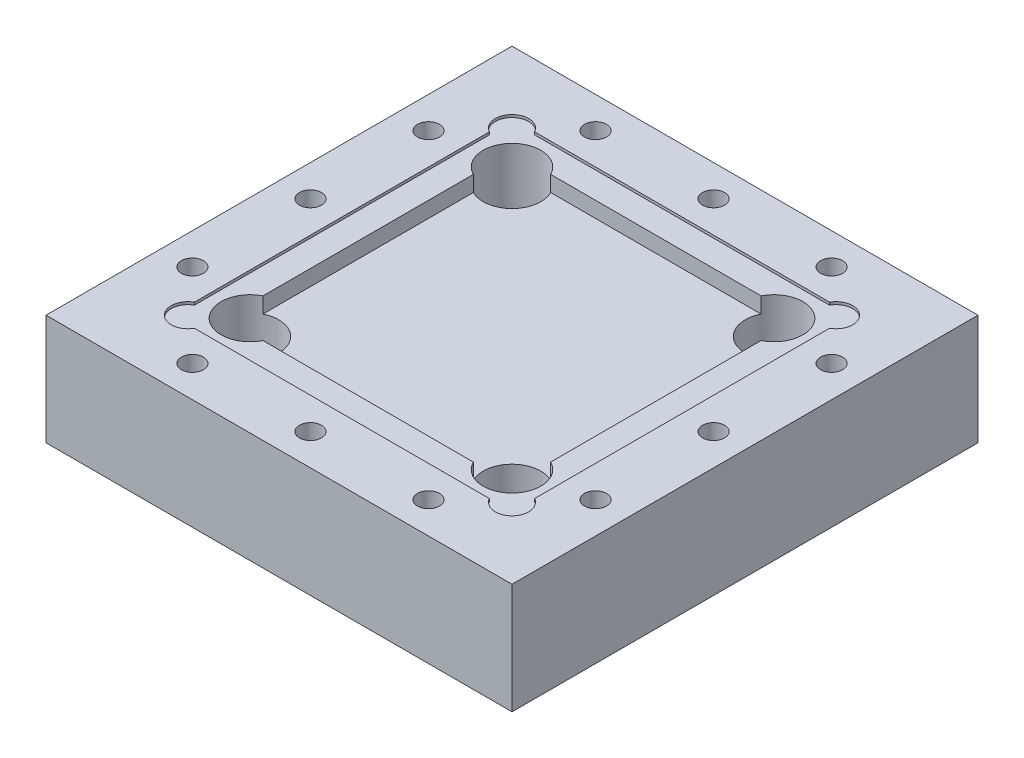
SolidWorks part; units mm, degrees
ref_plane "Front Plane" through (0, 0, 0) normal (0, 0, 1) x (1, 0, 0)
ref_plane "Top Plane" through (0, 0, 0) normal (0, 1, 0) x (1, 0, 0)
ref_plane "Right Plane" through (0, 0, 0) normal (1, 0, 0) x (0, 0, -1)
sketch "Sketch1" plane through (0, 0, 0) normal (0, 1, 0) x (1, 0, 0)
  line L0 (-38.45, 38.45) -> (-22.5235, 38.45) construction
  line L1 (-25, -25) -> (25, -25) construction
  line L2 (-25, -25) -> (-25, 25) construction
  line L3 (-25, 25) -> (25, 25) construction
  line L4 (25, -25) -> (25, 25) construction
  line L5 (-25, -25) -> (25, 25) construction
  line L6 (-25, 25) -> (25, -25) construction
  line L7 (44.45, -44.45) -> (-44.45, -44.45)
  line L8 (44.45, -44.45) -> (44.45, 44.45)
  line L9 (44.45, 44.45) -> (-44.45, 44.45)
  line L10 (-44.45, -44.45) -> (-44.45, 44.45)
  line L11 (44.45, -44.45) -> (-44.45, 44.45) construction
  line L12 (44.45, 44.45) -> (-44.45, -44.45) construction
  line L13 (32.45, -32.45) -> (-32.45, -32.45) construction
  line L14 (32.45, -32.45) -> (32.45, 32.45) construction
  line L15 (32.45, 32.45) -> (-32.45, 32.45) construction
  line L16 (-32.45, -32.45) -> (-32.45, 32.45) construction
  line L17 (32.45, -32.45) -> (-32.45, 32.45) construction
  line L18 (32.45, 32.45) -> (-32.45, -32.45) construction
  line L19 (-22.5235, 38.45) -> (0, 38.45) construction
  line L20 (0, 38.45) -> (22.5235, 38.45) construction
  line L21 (22.5235, 38.45) -> (38.45, 38.45) construction
  line L22 (38.45, 38.45) -> (38.45, 22.5235) construction
  line L23 (38.45, 22.5235) -> (38.45, 0) construction
  line L24 (38.45, 0) -> (38.45, -22.5235) construction
  line L25 (38.45, -22.5235) -> (38.45, -38.45) construction
  line L26 (38.45, -38.45) -> (22.5235, -38.45) construction
  line L27 (22.5235, -38.45) -> (0, -38.45) construction
  line L28 (0, -38.45) -> (-22.5235, -38.45) construction
  line L29 (-22.5235, -38.45) -> (-38.45, -38.45) construction
  line L30 (-38.45, -38.45) -> (-38.45, -22.5235) construction
  line L31 (-38.45, -22.5235) -> (-38.45, 0) construction
  line L32 (-38.45, 0) -> (-38.45, 22.5235) construction
  line L33 (-38.45, 22.5235) -> (-38.45, 38.45) construction
  line L34 (-38.45, 22.5235) -> (-22.5235, 38.45) construction
  line L35 (22.5235, 38.45) -> (38.45, 22.5235) construction
  line L36 (38.45, -22.5235) -> (22.5235, -38.45) construction
  line L37 (-38.45, -22.5235) -> (-22.5235, -38.45) construction
  line L38 (-32.45, 0) -> (-44.45, 0) construction
  line L40 (27.45, -27.45) -> (-27.45, -27.45) construction
  line L41 (27.45, -27.45) -> (27.45, 27.45) construction
  line L42 (27.45, 27.45) -> (-27.45, 27.45) construction
  line L43 (-27.45, -27.45) -> (-27.45, 27.45) construction
  line L44 (27.45, -27.45) -> (-27.45, 27.45) construction
  line L45 (27.45, 27.45) -> (-27.45, -27.45) construction
  circle A0 centre (-25, 25) radius 5 construction
  circle A1 centre (25, 25) radius 5 construction
  circle A2 centre (25, -25) radius 5 construction
  circle A3 centre (-25, -25) radius 5 construction
  circle A4 centre (-22.5235, 38.45) radius 4.25 construction
  circle A5 centre (0, 38.45) radius 4.25 construction
  circle A6 centre (22.5235, 38.45) radius 4.25 construction
  circle A7 centre (38.45, 22.5235) radius 4.25 construction
  circle A8 centre (38.45, 0) radius 4.25 construction
  circle A9 centre (38.45, -22.5235) radius 4.25 construction
  circle A10 centre (22.5235, -38.45) radius 4.25 construction
  circle A11 centre (0, -38.45) radius 4.25 construction
  circle A12 centre (-22.5235, -38.45) radius 4.25 construction
  circle A13 centre (-38.45, -22.5235) radius 4.25 construction
  circle A14 centre (-38.45, 0) radius 4.25 construction
  circle A15 centre (-38.45, 22.5235) radius 4.25 construction
  point P0 (0, 0)
  point P6 (0, 0)
  point P11 (0, 0)
  point P51 (0, 0)
  dimension "D4" = 10
  dimension "D5" = 8.5
  dimension "D1" = 50
  dimension "D2" = 64.9
  dimension "D3" = 12
  dimension "D6" = 5
  dimension "D7" = 88.9
extrude "Boss-Extrude1" add sketch "Sketch1" along normal blind 21.082
sketch "Sketch2" plane through (0, 21.082, 0) normal (0, 1, 0) x (1, 0, 0)
  line L0 (32.45, -32.45) -> (-32.45, -32.45) construction
  line L1 (32.45, -32.45) -> (32.45, 32.45) construction
  line L2 (-32.45, -32.45) -> (-32.45, 32.45) construction
  line L3 (32.45, 32.45) -> (-32.45, 32.45) construction
  line L4 (28.1344, -32.45) -> (-28.1344, -32.45)
  line L5 (32.45, -28.1344) -> (32.45, 28.1344)
  line L6 (-32.45, -28.1344) -> (-32.45, 28.1344)
  line L7 (28.1344, 32.45) -> (-28.1344, 32.45)
  line L8 (44.45, -44.45) -> (-44.45, 44.45) construction
  line L9 (-32.45, 32.45) -> (-33.1571, 33.1571) construction
  line L10 (44.45, 44.45) -> (-44.45, -44.45) construction
  line L11 (32.45, 32.45) -> (33.1571, 33.1571) construction
  line L12 (32.45, -32.45) -> (33.1571, -33.1571) construction
  line L13 (-32.45, -32.45) -> (-33.1571, -33.1571) construction
  arc A0 (-28.1344, 32.45) -> (-32.45, 28.1344) centre (-30.912, 30.912) ccw
  arc A1 (32.45, 28.1344) -> (28.1344, 32.45) centre (30.912, 30.912) ccw
  arc A2 (28.1344, -32.45) -> (32.45, -28.1344) centre (30.912, -30.912) ccw
  arc A3 (-32.45, -28.1344) -> (-28.1344, -32.45) centre (-30.912, -30.912) ccw
  dimension "D2" = 6.35
  dimension "D1" = 1
extrude "Cut-Extrude1" cut sketch "Sketch2" against normal blind 0.5
sketch "Sketch3" plane through (0, 20.582, 0) normal (0, 1, 0) x (1, 0, 0)
  line L0 (27.45, -27.45) -> (27.45, 27.45) construction
  line L1 (27.45, -27.45) -> (-27.45, -27.45) construction
  line L2 (-27.45, -27.45) -> (-27.45, 27.45) construction
  line L3 (27.45, 27.45) -> (-27.45, 27.45) construction
  line L4 (27.45, -27.45) -> (27.45, 27.45)
  line L5 (27.45, -27.45) -> (-27.45, -27.45)
  line L6 (-27.45, -27.45) -> (-27.45, 27.45)
  line L7 (27.45, 27.45) -> (-27.45, 27.45)
extrude "Cut-Extrude2" cut sketch "Sketch3" against normal blind 3
fillet "Fillet1" radius 6.35 4 edges at (-27.45, 19.082, 27.45) (27.45, 19.082, 27.45) (27.45, 19.082, -27.45) (-27.45, 19.082, -27.45)
hole_wizard "CBORE for M6 SHCS1" positions "Sketch4" profile "Sketch5" counterbore size "M6" standard "ANSI Metric" end condition through all
sketch "Sketch4" plane through (0, 21.082, 0) normal (0, 1, 0) x (1, 0, 0)
  point P0 (-25, 25)
  point P3 (25, 25)
  point P6 (25, -25)
  point P9 (-25, -25)
sketch "Sketch5" plane through (-25, 21.082, -25) normal (1, 0, 0) x (0, 0, 1)
  line L0 (0, 0) -> (0, 21.082)
  line L1 (0, 21.082) -> (3.3, 21.082)
  line L3 (3.3, 21.082) -> (3.3, 14.7376)
  line L4 (3.3, 14.7376) -> (5.5, 14.7376)
  line L5 (5.5, 14.7376) -> (5.5, 0)
  line L7 (5.5, 0) -> (0, 0)
  line L11 (0, -6.35) -> (0, 107.95) construction
  dimension "Thru Hole Dia." = 6.6
  dimension "Thru Hole Depth" = 21.082
  dimension "C'Bore Dia." = 11
  dimension "C'Bore Depth" = 14.7376
hole_wizard "M5x0.8 Tapped Hole1" positions "Sketch6" profile "Sketch7" tap size "M5x0.8" standard "ANSI Metric" end condition through all
sketch "Sketch6" plane through (0, 21.082, 0) normal (0, 1, 0) x (1, 0, 0)
  point P0 (-38.45, 22.5235)
  point P3 (-38.45, 0)
  point P6 (-38.45, -22.5235)
  point P9 (-22.5235, -38.45)
  point P12 (0, -38.45)
  point P15 (22.5235, -38.45)
  point P18 (38.45, -22.5235)
  point P21 (38.45, 0)
  point P24 (38.45, 22.5235)
  point P27 (22.5235, 38.45)
  point P30 (0, 38.45)
  point P33 (-22.5235, 38.45)
sketch "Sketch7" plane through (-38.45, 21.082, -22.5235) normal (1, 0, 0) x (0, 0, 1)
  line L0 (0, 0) -> (0, 21.082)
  line L1 (0, 21.082) -> (2.1, 21.082)
  line L2 (2.1, 21.082) -> (2.1, 0)
  line L5 (2.1, 0) -> (0, 0)
  line L11 (0, -6.35) -> (0, 107.95) construction
  dimension "Thru Tap Drill Dia." = 4.2
  dimension "Thru Tap Drill Depth" = 21.082
cosmetic thread "Hole Thread1" parameters "D2"=5
cosmetic thread "Hole Thread2" parameters "D2"=5
cosmetic thread "Hole Thread3" parameters "D2"=5
cosmetic thread "Hole Thread4" parameters "D2"=5
cosmetic thread "Hole Thread5" parameters "D2"=5
cosmetic thread "Hole Thread6" parameters "D2"=5
cosmetic thread "Hole Thread7" parameters "D2"=5
cosmetic thread "Hole Thread8" parameters "D2"=5
cosmetic thread "Hole Thread9" parameters "D2"=5
cosmetic thread "Hole Thread10" parameters "D2"=5
cosmetic thread "Hole Thread11" parameters "D2"=5
cosmetic thread "Hole Thread12" parameters "D2"=5
